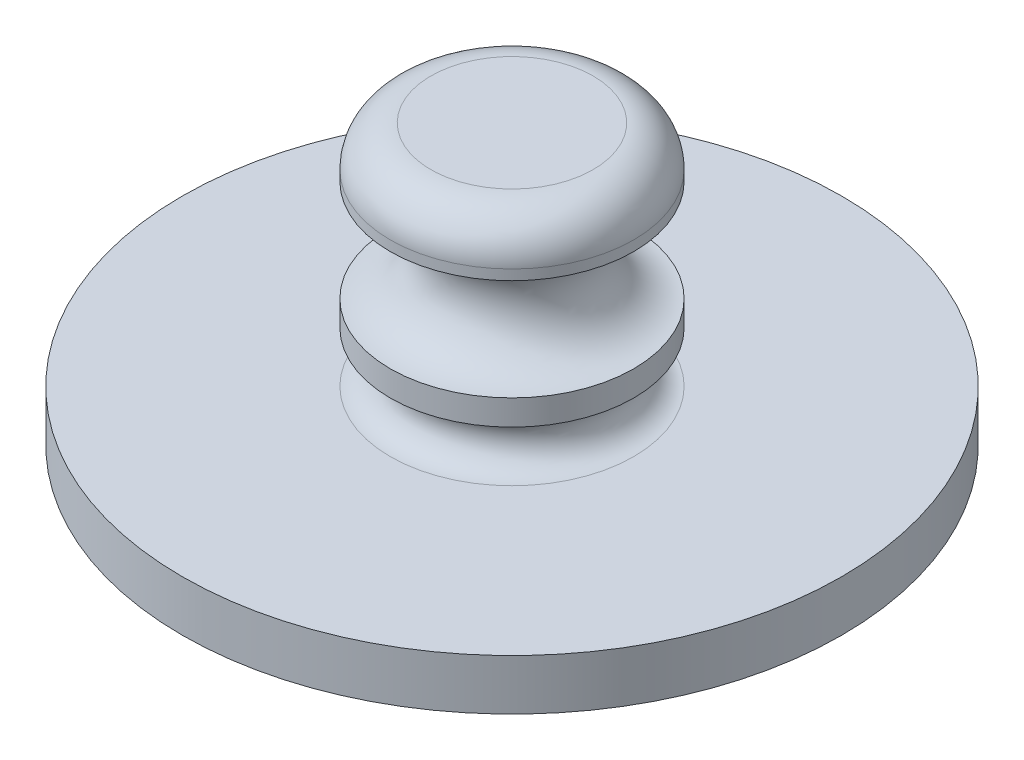
SolidWorks part; units mm, degrees
ref_plane "Front Plane" through (0, 0, 0) normal (0, 0, 1) x (1, 0, 0)
ref_plane "Top Plane" through (0, 0, 0) normal (0, 1, 0) x (1, 0, 0)
ref_plane "Right Plane" through (0, 0, 0) normal (1, 0, 0) x (0, 0, -1)
sketch "Sketch1" plane through (0, 0, 0) normal (0, 0, 1) x (1, 0, 0)
  line L0 (0, 0) -> (0, 77101.525) construction
  line L2 (0, 0) -> (6.5, 0)
  line L3 (0, 0) -> (0, 1)
  line L4 (2.4, 1) -> (6.5, 1)
  line L5 (6.5, 0) -> (6.5, 1)
  line L6 (0, 1) -> (0, 5.5)
  line L7 (0, 5.5) -> (1.6, 5.5)
  line L8 (2.4, 2) -> (2.4, 2.5)
  line L9 (2.4, 4.5) -> (2.4, 4.7)
  line L10 (0, 1) -> (2.4, 1) construction
  arc A0 (2.4, 1) -> (2.4, 2) centre (2.4, 1.5) cw
  arc A1 (2.4, 2.5) -> (2.4, 4.5) centre (2.4, 3.5) cw
  arc A2 (1.6, 5.5) -> (2.4, 4.7) centre (1.6, 4.7) cw
  point P7 (-1.7241, 5.5)
  point P15 (1.332, 3.1176)
  point P19 (2.4, 5.5)
  point P20 (1.4, 3.5)
  point P21 (0, 5.5)
  dimension "D8" = 0.8
  dimension "D1" = 1
  dimension "D2" = 6.5
  dimension "D3" = 1.4
  dimension "D4" = 1
  dimension "D5" = 2
  dimension "D6" = 0.5
  dimension "D7" = 1
revolve "Revolve1" add sketch "Sketch1" angle 360 about L0 region at (1.9618, 2.0746, 0)
